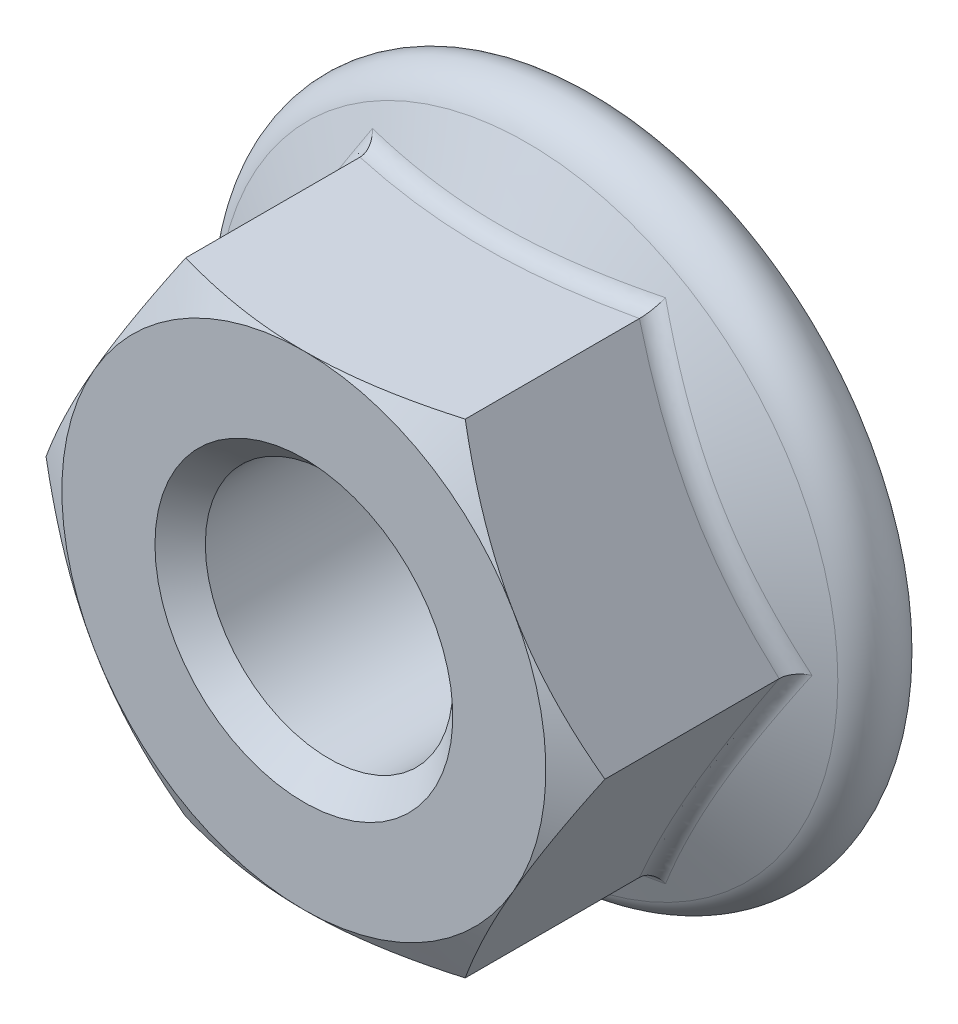
SolidWorks part; units mm, degrees
ref_plane "Front" through (0, 0, 0) normal (0, 0, 1) x (1, 0, 0)
ref_plane "Top" through (0, 0, 0) normal (0, 1, 0) x (1, 0, 0)
ref_plane "Right" through (0, 0, 0) normal (1, 0, 0) x (0, 0, -1)
sketch "Sketch1" plane through (0, 0, 0) normal (0, 0, 1) x (1, 0, 0)
  line L1 (3.7528, -6.5) -> (7.5056, 0)
  line L2 (7.5056, 0) -> (3.7528, 6.5)
  line L3 (3.7528, 6.5) -> (-3.7528, 6.5)
  line L4 (-3.7528, 6.5) -> (-7.5056, 0)
  line L5 (-7.5056, 0) -> (-3.7528, -6.5)
  line L6 (-3.7528, -6.5) -> (3.7528, -6.5)
  circle A0 centre (0, 0) radius 6.5 construction
  circle A1 centre (0, 0) radius 3.3235
  dimension "D1" = 6.647
extrude "BaseNut" add sketch "Sketch1" against normal blind 8
cosmetic thread "ThreadCosmetic1" [suppressed] parameters "D2"=8
sketch "Sketch3" plane through (0.6779, 0, -16.6426) normal (0, 1, 0) x (0, 0, -1)
  line L0 (4.0352, 0.6779) -> (-19.0613, 0.6779) construction
  line L2 (-16.6426, 7.1779) -> (-16.0621, 8.1834)
  line L4 (-16.0621, 8.1834) -> (-16.6426, 8.1834)
  line L5 (-16.6426, 8.1834) -> (-16.6426, 7.1779)
  line L6 (-12.6426, 8.1834) -> (-12.6426, 14.238) construction
  line L8 (-8.6426, 8.1834) -> (-8.6426, 7.1779)
  line L9 (-9.2232, 8.1834) -> (-8.6426, 8.1834)
  line L10 (-8.6426, 7.1779) -> (-9.2232, 8.1834)
  line L11 (-8.6426, 8.1834) -> (-16.6426, 8.1834) construction
  dimension "D1" = 30
revolve "Double-Chamfer" cut sketch "Sketch3" angle 360 about L0
sketch "Sketch4" plane through (4.6827, 0, -16.7173) normal (0, 1, 0) x (0, 0, -1)
  line L0 (-21.7744, 4.6827) -> (9.7398, 4.6827) construction
  line L2 (-13.0599, 30.5008) -> (-13.0599, 8.9315) construction
  line L3 (-10.7189, 13.0264) -> (-13.0599, 8.0062)
  line L4 (-8.7173, 8.0062) -> (-16.7173, 8.0062) construction
  line L5 (-8.7173, 8.0062) -> (-8.7173, 12.5827)
  line L11 (-13.0599, 8.0062) -> (-8.7173, 8.0062)
  arc A0 (-8.7173, 12.5827) -> (-10.7189, 13.0264) centre (-9.7673, 12.5827) ccw
  dimension "dc" = 17.9
  dimension "m1" = 8
revolve "Flange" add sketch "Sketch4" angle 360 about L0
fillet "FlangeFillet" radius 0.5 6 edges at (-4.7562, -4.7621, -5.2461) (-6.5022, 1.7379, -5.2461) (4.7562, 4.7621, -5.2461) (6.5022, -1.7379, -5.2461)
sketch "Sketch5" plane through (-5.1971, 0, -15.1971) normal (0, 1, 0) x (0, 0, -1)
  line L0 (3.5984, -5.1971) -> (-23.9926, -5.1971) construction
  line L1 (-7.1971, -1.8736) -> (-15.1971, -1.8736) construction
  line L2 (-15.1971, -1.1971) -> (-15.1971, -1.8736)
  line L4 (-15.1971, -1.8736) -> (-14.5206, -1.8736)
  line L6 (-14.5206, -1.8736) -> (-15.1971, -1.1971)
  line L7 (-11.1971, -1.8736) -> (-11.1971, 0.9419) construction
  line L8 (-7.8736, -1.8736) -> (-7.1971, -1.1971)
  line L9 (-7.1971, -1.8736) -> (-7.8736, -1.8736)
  line L10 (-7.1971, -1.1971) -> (-7.1971, -1.8736)
  dimension "da" = 8
  dimension "D2" = 45
revolve "Hole" cut sketch "Sketch5" angle 360 about L0
sketch "Sketch6" plane through (0, 0, 0) normal (0, 1, 0) x (1, 0, 0)
  line L0 (-3.9094, 0.6765) -> (-3.3235, 0.3383)
  line L1 (-3.3235, 0.3383) -> (-2.647, 0.3383)
  line L2 (-2.647, 0.3383) -> (-2.647, 1.0148)
  line L3 (-2.647, 1.0148) -> (-3.3235, 1.0148)
  line L4 (-3.3235, 1.0148) -> (-3.9094, 0.6765)
  line L5 (0, 7.348) -> (0, 34.1252) construction
  dimension "D1" = 0.6765
  dimension "D2" = 6.647
revolve "Cut-Revolve10" [suppressed] cut sketch "Sketch6" angle 360 about L5
pattern_linear "LPattern10" [suppressed] count 10 spacing 0.8118 along (0, 0, -1) of bodies 105
equation "\"m1@Sketch4\" = \"m@BaseNut\""
equation "\"sq@Sketch3\" = \"s@Sketch1\""
equation "\"D2@Sketch6\"=\"D1@Sketch1\""
equation "\"D1@Sketch6\"= (\"D2@ThreadCosmetic1\"  - \"D2@Sketch6\" )  / 2"
equation "\"D3@LPattern10\"=\"D1@Sketch6\" * 1.2 "
equation "\"D1@LPattern10\"=\"m@BaseNut\"  / \"D3@LPattern10\""
